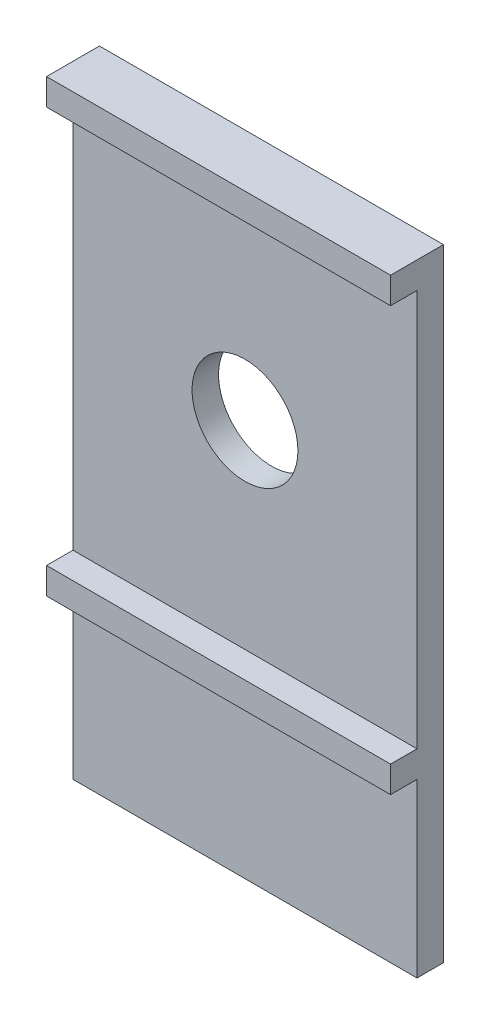
SolidWorks part; units mm, degrees
ref_plane "Přední rovina" through (0, 0, 0) normal (0, 0, 1) x (1, 0, 0)
ref_plane "Horní rovina" through (0, 0, 0) normal (0, 1, 0) x (1, 0, 0)
ref_plane "Pravá rovina" through (0, 0, 0) normal (1, 0, 0) x (0, 0, -1)
sketch "Skica1" plane through (0, 0, 0) normal (0, 0, 1) x (1, 0, 0)
  line L1 (0, 0) -> (13, 0)
  line L2 (0, 0) -> (0, 23.5)
  line L3 (0, 23.5) -> (13, 23.5)
  line L4 (13, 0) -> (13, 23.5)
  dimension "D1" = 13
  dimension "D2" = 23.5
extrude "Přidat vysunutím1" add sketch "Skica1" along normal blind 1
sketch "Skica2" plane through (0, 0, 1) normal (0, 0, 1) x (1, 0, 0)
  line L0 (13, 0) -> (13, 23.5) construction
  line L1 (0, 23.5) -> (13, 23.5)
  line L2 (0, 23.5) -> (0, 22.5)
  line L3 (0, 22.5) -> (13, 22.5)
  line L4 (13, 23.5) -> (13, 22.5)
  line L5 (0, 23.5) -> (0, 0) construction
  line L6 (0, 7.5) -> (13, 7.5)
  line L7 (0, 7.5) -> (0, 6.5)
  line L8 (0, 6.5) -> (13, 6.5)
  line L9 (13, 7.5) -> (13, 6.5)
  dimension "D1" = 1
  dimension "D2" = 1
  dimension "D3" = 15
extrude "Přidat vysunutím2" add sketch "Skica2" along normal blind 1
sketch "Skica3" plane through (0, 0, 1) normal (0, 0, 1) x (1, 0, 0)
  line L0 (13, 7.5) -> (0, 7.5) construction
  line L3 (0, 22.5) -> (0, 7.5) construction
  circle A0 centre (6.5, 15) radius 2
  dimension "D1" = 4
  dimension "D2" = 7.5
  dimension "D3" = 6.5
extrude "Odebrat vysunutím1" cut sketch "Skica3" against normal blind 1
